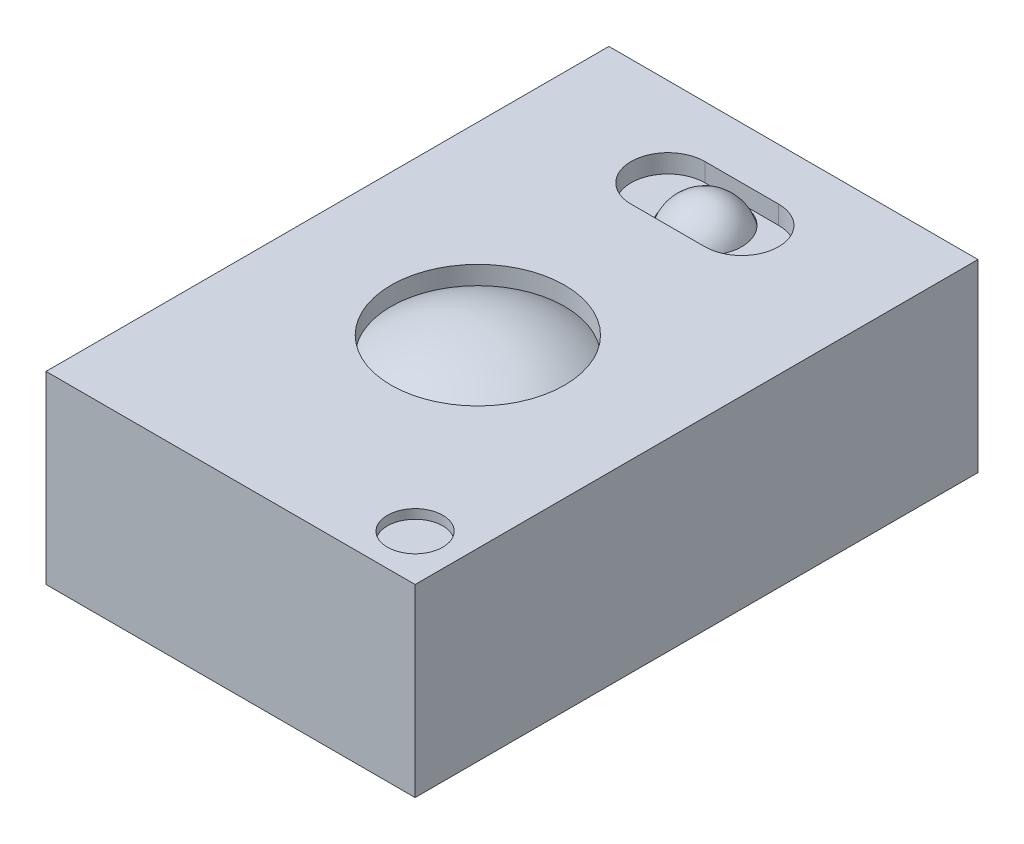
SolidWorks part; units mm, degrees
ref_plane "Front Plane" through (0, 0, 0) normal (0, 0, 1) x (1, 0, 0)
ref_plane "Top Plane" through (0, 0, 0) normal (0, 1, 0) x (1, 0, 0)
ref_plane "Right Plane" through (0, 0, 0) normal (1, 0, 0) x (0, 0, -1)
sketch "Sketch1" plane through (0, 0, 0) normal (0, 1, 0) x (1, 0, 0)
  line L1 (-1, -1.525) -> (1, -1.525)
  line L2 (-1, -1.525) -> (-1, 1.525)
  line L3 (-1, 1.525) -> (1, 1.525)
  line L4 (1, -1.525) -> (1, 1.525)
  line L5 (-1, -1.525) -> (1, 1.525) construction
  line L6 (-1, 1.525) -> (1, -1.525) construction
  point P0 (0, 0)
  dimension "D1" = 3.05
  dimension "D2" = 2
extrude "Boss-Extrude1" add sketch "Sketch1" along normal blind 1
sketch "Sketch2" plane through (0, 1, 0) normal (0, 1, 0) x (1, 0, 0)
  line L0 (-1, -1.525) -> (1, -1.525) construction
  line L1 (-0.2, 1.045) -> (0.2, 1.045) construction
  line L2 (-0.2, 1.245) -> (0.2, 1.245)
  line L3 (-0.2, 0.845) -> (0.2, 0.845)
  circle A0 centre (0, -0.185) radius 0.47
  arc A1 (-0.2, 1.245) -> (-0.2, 0.845) centre (-0.2, 1.045) ccw
  arc A2 (0.2, 0.845) -> (0.2, 1.245) centre (0.2, 1.045) ccw
  point P6 (0, 1.045)
  point P11 (0, 0)
  dimension "D3" = 0.4
  dimension "D4" = 0.94
  dimension "D1" = 1.34
  dimension "D2" = 0.4
  dimension "D5" = 1.23
extrude "Cut-Extrude1" cut sketch "Sketch2" against normal blind 0.1
sketch "Sketch3" plane through (0, 1, 0) normal (0, 1, 0) x (1, 0, 0)
  line L0 (-1, -1.525) -> (1, -1.525) construction
  line L1 (1, -1.525) -> (1, 1.525) construction
  circle A0 centre (0.75, -1.275) radius 0.15
  dimension "D1" = 0.3
  dimension "D3" = 0.25
  dimension "D2" = 0.25
extrude "Cut-Extrude2" cut sketch "Sketch3" against normal blind 0.05
dome "Dome1" faces to dome 1 distance 0.15 reverse direction no elliptical dome no face at (0, 0.9, 0.655) parameters "D1"=0.15
sketch "Sketch5" plane through (0, 0.9, 0) normal (0, 1, 0) x (1, 0, 0)
  circle A0 centre (0, 1.045) radius 0.2
extrude "Cut-Extrude3" cut sketch "Sketch5" against normal blind 0.01
dome "Dome2" faces to dome 1 distance 0.15 reverse direction no elliptical dome no face at (0, 0.89, -0.845) parameters "D1"=0.15
sketch "Sketch6" plane through (0, 0, 0) normal (0, -1, 0) x (1, 0, 0)
  line L0 (0, -1.5861) -> (0, 1.7433) construction
  line L1 (0.925, -1.45) -> (0.425, -1.45)
  line L2 (0.925, -1.45) -> (0.925, -0.875)
  line L3 (0.925, -0.875) -> (0.425, -0.875)
  line L4 (0.425, -1.45) -> (0.425, -0.875)
  line L53 (0.925, -0.67) -> (0.925, -0.095)
  line L54 (0.925, -0.67) -> (0.425, -0.67)
  line L55 (0.425, -0.67) -> (0.425, -0.095)
  line L56 (0.925, -0.095) -> (0.425, -0.095)
  line L57 (0.925, 0.11) -> (0.925, 0.685)
  line L58 (0.925, 0.11) -> (0.425, 0.11)
  line L59 (0.425, 0.11) -> (0.425, 0.685)
  line L60 (0.925, 0.685) -> (0.425, 0.685)
  line L61 (0.925, 0.89) -> (0.925, 1.465)
  line L62 (0.925, 0.89) -> (0.6353, 0.89)
  line L63 (0.425, 1.1183) -> (0.425, 1.465)
  line L64 (0.925, 1.465) -> (0.425, 1.465)
  line L65 (0.6353, 0.89) -> (0.425, 1.1183)
  line L66 (-1.2213, 0) -> (1.5976, 0) construction
  line L67 (-0.925, 0.89) -> (-0.425, 0.89)
  line L68 (-0.425, 0.89) -> (-0.425, 1.465)
  line L69 (-0.925, 1.465) -> (-0.425, 1.465)
  line L70 (-0.925, 0.89) -> (-0.925, 1.465)
  line L71 (-0.925, 0.11) -> (-0.425, 0.11)
  line L72 (-0.425, 0.11) -> (-0.425, 0.685)
  line L73 (-0.925, 0.685) -> (-0.425, 0.685)
  line L74 (-0.925, 0.11) -> (-0.925, 0.685)
  line L75 (-0.925, -0.67) -> (-0.425, -0.67)
  line L76 (-0.425, -0.67) -> (-0.425, -0.095)
  line L77 (-0.925, -0.095) -> (-0.425, -0.095)
  line L78 (-0.925, -0.67) -> (-0.925, -0.095)
  line L79 (-0.925, -0.875) -> (-0.425, -0.875)
  line L80 (-0.425, -1.45) -> (-0.425, -0.875)
  line L81 (-0.925, -1.45) -> (-0.425, -1.45)
  line L82 (-0.925, -1.45) -> (-0.925, -0.875)
  line L84 (0.925, -11.45) -> (0.925, -10.875) [skipped]
  line L85 (0.925, -11.45) -> (0.425, -11.45) [skipped]
  line L86 (0.425, -11.45) -> (0.425, -10.875) [skipped]
  line L87 (0.925, -10.875) -> (0.425, -10.875) [skipped]
  line L88 (0.925, -21.45) -> (0.925, -20.875) [skipped]
  line L89 (0.925, -21.45) -> (0.425, -21.45) [skipped]
  line L90 (0.425, -21.45) -> (0.425, -20.875) [skipped]
  line L91 (0.925, -20.875) -> (0.425, -20.875) [skipped]
  line L92 (0.925, -31.45) -> (0.925, -30.875) [skipped]
  line L93 (0.925, -31.45) -> (0.425, -31.45) [skipped]
  line L94 (0.425, -31.45) -> (0.425, -30.875) [skipped]
  line L95 (0.925, -30.875) -> (0.425, -30.875) [skipped]
  line L96 (0.925, -10.67) -> (0.925, -10.095) [skipped]
  line L97 (0.925, -10.67) -> (0.425, -10.67) [skipped]
  line L98 (0.425, -10.67) -> (0.425, -10.095) [skipped]
  line L99 (0.925, -10.095) -> (0.425, -10.095) [skipped]
  line L100 (0.925, -20.67) -> (0.925, -20.095) [skipped]
  line L101 (0.925, -20.67) -> (0.425, -20.67) [skipped]
  line L102 (0.425, -20.67) -> (0.425, -20.095) [skipped]
  line L103 (0.925, -20.095) -> (0.425, -20.095) [skipped]
  line L104 (0.925, -30.67) -> (0.925, -30.095) [skipped]
  line L105 (0.925, -30.67) -> (0.425, -30.67) [skipped]
  line L106 (0.425, -30.67) -> (0.425, -30.095) [skipped]
  line L107 (0.925, -30.095) -> (0.425, -30.095) [skipped]
  line L108 (0.925, -9.89) -> (0.925, -9.315) [skipped]
  line L109 (0.925, -9.89) -> (0.425, -9.89) [skipped]
  line L110 (0.425, -9.89) -> (0.425, -9.315) [skipped]
  line L111 (0.925, -9.315) -> (0.425, -9.315) [skipped]
  line L112 (0.925, -19.89) -> (0.925, -19.315) [skipped]
  line L113 (0.925, -19.89) -> (0.425, -19.89) [skipped]
  line L114 (0.425, -19.89) -> (0.425, -19.315) [skipped]
  line L115 (0.925, -19.315) -> (0.425, -19.315) [skipped]
  line L116 (0.925, -29.89) -> (0.925, -29.315) [skipped]
  line L117 (0.925, -29.89) -> (0.425, -29.89) [skipped]
  line L118 (0.425, -29.89) -> (0.425, -29.315) [skipped]
  line L119 (0.925, -29.315) -> (0.425, -29.315) [skipped]
  line L120 (0.925, -9.11) -> (0.925, -8.535) [skipped]
  line L121 (0.925, -9.11) -> (0.425, -9.11) [skipped]
  line L122 (0.425, -9.11) -> (0.425, -8.535) [skipped]
  line L123 (0.925, -8.535) -> (0.425, -8.535) [skipped]
  line L124 (0.925, -19.11) -> (0.925, -18.535) [skipped]
  line L125 (0.925, -19.11) -> (0.425, -19.11) [skipped]
  line L126 (0.425, -19.11) -> (0.425, -18.535) [skipped]
  line L127 (0.925, -18.535) -> (0.425, -18.535) [skipped]
  line L128 (0.925, -29.11) -> (0.925, -28.535) [skipped]
  line L129 (0.925, -29.11) -> (0.425, -29.11) [skipped]
  line L130 (0.425, -29.11) -> (0.425, -28.535) [skipped]
  line L131 (0.925, -28.535) -> (0.425, -28.535) [skipped]
  dimension "D1" = 0.5
  dimension "D2" = 0.575
  dimension "D3" = 0.425
  dimension "D6" = 0.875
  dimension "D4" = 4
  dimension "D5" = 4
extrude "Boss-Extrude2" add sketch "Sketch6" along normal blind 0.01
